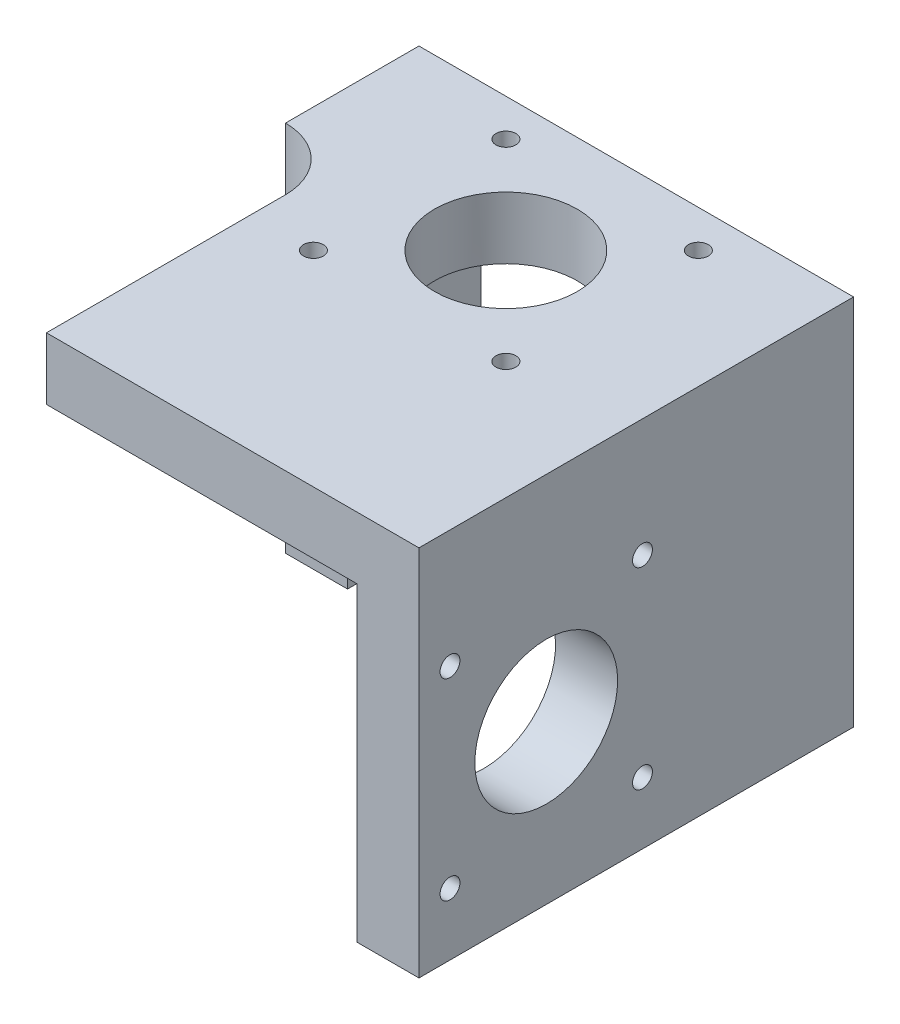
SolidWorks part; units mm, degrees
ref_plane "前视基准面" through (0, 0, 0) normal (0, 0, 1) x (1, 0, 0)
ref_plane "上视基准面" through (0, 0, 0) normal (0, 1, 0) x (1, 0, 0)
ref_plane "右视基准面" through (0, 0, 0) normal (1, 0, 0) x (0, 0, -1)
sketch "草图1" plane through (0, 0, 0) normal (0, 0, 1) x (1, 0, 0)
  line L1 (-47.5, 20.0735) -> (12.5, 20.0735)
  line L2 (-47.5, 20.0735) -> (-47.5, 10.0735)
  line L3 (-47.5, 10.0735) -> (2.5, 10.0735)
  line L4 (12.5, 20.0735) -> (12.5, 10.0735)
  line L5 (12.5, 20.0735) -> (2.5, 20.0735)
  line L6 (12.5, 20.0735) -> (12.5, -39.9265)
  line L7 (12.5, -39.9265) -> (2.5, -39.9265)
  line L8 (2.5, 10.0735) -> (2.5, -39.9265)
  dimension "D1" = 10
  dimension "D2" = 10
  dimension "D3" = 60
  dimension "D4" = 60
extrude "凸台-拉伸1" add sketch "草图1" along normal blind 70 contours L3 L8 L7 L6 L4 L1 L2 region at (-22.5, 19.225, 0)
sketch "草图2" plane through (0, 10.0735, 0) normal (0, -1, 0) x (1, 0, 0)
  line L0 (-47.5, 0) -> (2.5, 0) construction
  line L1 (-37.5, 37) -> (-6.5, 37) construction
  line L2 (-37.5, 37) -> (-37.5, 6) construction
  line L3 (-37.5, 6) -> (-6.5, 6) construction
  line L4 (-6.5, 37) -> (-6.5, 6) construction
  line L5 (-47.5, 70) -> (-47.5, 0) construction
  line L6 (-37.5, 37) -> (-6.5, 6) construction
  line L7 (-22, 21.5) -> (-22, 0) construction
  circle A0 centre (-37.5, 37) radius 1.6
  circle A1 centre (-37.5, 6) radius 1.6
  circle A2 centre (-6.5, 6) radius 1.6
  circle A3 centre (-6.5, 37) radius 1.6
  circle A4 centre (-22, 21.5) radius 11.5
  dimension "D3" = 3.2
  dimension "D6" = 23
  dimension "D1" = 31
  dimension "D2" = 31
  dimension "D4" = 6
  dimension "D5" = 10
extrude "切除-拉伸1" cut sketch "草图2" against normal blind 60
sketch "草图4" plane through (2.5, 0, 0) normal (-1, 0, 0) x (0, 0, 1)
  line L0 (70, 10.0735) -> (70, -39.9265) construction
  line L1 (34, 1.0735) -> (65, 1.0735) construction
  line L2 (34, 1.0735) -> (34, -29.9265) construction
  line L3 (34, -29.9265) -> (65, -29.9265) construction
  line L4 (65, 1.0735) -> (65, -29.9265) construction
  line L5 (70, -39.9265) -> (0, -39.9265) construction
  line L6 (34, 1.0735) -> (65, -29.9265) construction
  circle A0 centre (34, 1.0735) radius 1.6
  circle A1 centre (34, -29.9265) radius 1.6
  circle A2 centre (65, -29.9265) radius 1.6
  circle A3 centre (65, 1.0735) radius 1.6
  circle A4 centre (49.5, -14.4265) radius 11.5
  dimension "D3" = 3.2
  dimension "D6" = 23
  dimension "D1" = 31
  dimension "D2" = 31
  dimension "D4" = 5
  dimension "D5" = 10
extrude "切除-拉伸2" cut sketch "草图4" against normal blind 60
sketch "草图6" plane through (0, 0, 0) normal (0, 0, -1) x (-1, 0, 0)
  line L1 (47.5, 20.0735) -> (57.5, 20.0735)
  line L2 (47.5, 20.0735) -> (47.5, -39.9265)
  line L3 (47.5, -39.9265) -> (57.5, -39.9265)
  line L4 (57.5, 20.0735) -> (57.5, -39.9265)
  dimension "D1" = 10
  dimension "D2" = 60
extrude "凸台-拉伸2" add sketch "草图6" against normal blind 21.5
sketch "草图7" plane through (-57.5, 0, 0) normal (-1, 0, 0) x (0, 0, 1)
  line L0 (21.5, 10.0735) -> (21.5, -39.9265) construction
  line L1 (21.5, -39.9265) -> (21.5, 20.0735) construction
  line L2 (70, 10.0735) -> (0, 10.0735) construction
  line L3 (49.5, -2.9265) -> (49.5, -25.9265) construction
  line L4 (70, -39.9265) -> (0, -39.9265) construction
  circle A0 centre (21.5, -18.9265) radius 4.55
  circle A1 centre (49.5, -14.4265) radius 11.5 construction
  point P7 (21.5, -14.4265)
  point P16 (0, 0)
  point P17 (0, 0)
  dimension "D1" = 9.1
  dimension "D2" = 21
extrude "切除-拉伸3" cut sketch "草图7" against normal blind 20.5
fillet "圆角1" radius 10 1 edges at (-47.5, 15.0735, 21.5)
fillet "圆角2" radius 10 1 edges at (-52.5, 10.0735, 21.5)
